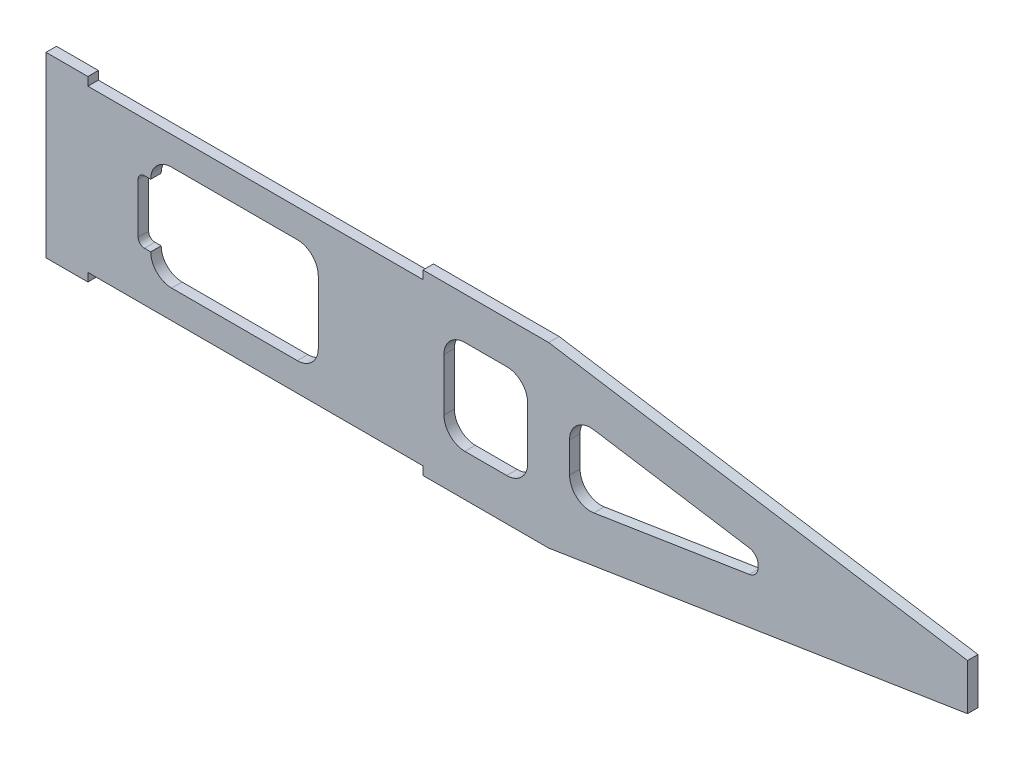
SolidWorks part; units mm, degrees
ref_plane "Ebene vorne" through (0, 0, 0) normal (0, 0, 1) x (1, 0, 0)
ref_plane "Ebene oben" through (0, 0, 0) normal (0, 1, 0) x (1, 0, 0)
ref_plane "Ebene rechts" through (0, 0, 0) normal (1, 0, 0) x (0, 0, -1)
sketch "Skizze1" plane through (0, 0, 0) normal (0, 0, 1) x (1, 0, 0)
  line L0 (0, 0) -> (440, 0) construction
  line L1 (0, 42.5) -> (0, -42.5)
  line L2 (0, -42.5) -> (240, -42.5)
  line L3 (240, -42.5) -> (440, -11)
  line L4 (440, -11) -> (440, 11)
  line L5 (240, 42.5) -> (440, 11)
  line L6 (0, 42.5) -> (240, 42.5)
  dimension "D1" = 440
  dimension "D2" = 85
  dimension "D3" = 22
  dimension "D4" = 200
extrude "Grundplatte" add sketch "Skizze1" along normal blind 5
sketch "Skizze2" plane through (0, 0, 5) normal (0, 0, 1) x (1, 0, 0)
  line L0 (50, 0) -> (44, 0) construction
  line L1 (130, 25) -> (50, 25)
  line L2 (130, 25) -> (130, -25)
  line L3 (130, -25) -> (50, -25)
  line L4 (50, 25) -> (50, 15)
  line L5 (130, 25) -> (50, -25) construction
  line L6 (130, -25) -> (50, 25) construction
  line L7 (44, -15) -> (44, 15)
  line L8 (44, 15) -> (50, 15)
  line L9 (44, -15) -> (50, -15)
  line L10 (50, -15) -> (50, -25)
  point P0 (90, 0)
  dimension "D1" = 90
  dimension "D2" = 50
  dimension "D3" = 80
  dimension "D4" = 30
  dimension "D5" = 6
extrude "Schnitt-Linear austragen1" cut sketch "Skizze2" against normal through all
fillet "Verrundung1" radius 10 4 edges at (130, 25, 2.5) (130, -25, 2.5) (50, 25, 2.5) (50, -25, 2.5)
sketch "Skizze3" plane through (0, 0, 5) normal (0, 0, 1) x (1, 0, 0)
  line L0 (0, 0) -> (440, 0) construction
  line L1 (0, 42.5) -> (0, -42.5) construction
  line L2 (440, -11) -> (440, 11) construction
  line L3 (240, 42.5) -> (0, 42.5) construction
  line L4 (20, 42.5) -> (180, 42.5)
  line L5 (20, 42.5) -> (20, 38.5)
  line L6 (20, 38.5) -> (180, 38.5)
  line L7 (180, 42.5) -> (180, 38.5)
  line L8 (180, -42.5) -> (180, -38.5)
  line L9 (20, -38.5) -> (180, -38.5)
  line L10 (20, -42.5) -> (20, -38.5)
  line L11 (20, -42.5) -> (180, -42.5)
  dimension "D1" = 4
  dimension "D2" = 160
  dimension "D3" = 20
extrude "Ausschnitt_Flächenaufdoppler" cut sketch "Skizze3" against normal through all
sketch "Skizze4" plane through (0, 0, 5) normal (0, 0, 1) x (1, 0, 0)
  line L0 (0, 0) -> (440, 0) construction
  line L1 (440, -11) -> (440, 11) construction
  line L2 (190, -22.5) -> (190, 22.5)
  line L3 (190, 22.5) -> (230, 22.5)
  line L4 (230, 22.5) -> (230, -22.5)
  line L6 (250, -19) -> (250, 19)
  line L7 (250, 19) -> (340, 4.825)
  line L8 (340, 4.825) -> (340, -4.825)
  line L9 (250, -19) -> (340, -4.825)
  line L10 (190, -22.5) -> (230, -22.5)
  line L11 (440, 11) -> (240, 42.5) construction
  line L13 (0, 42.5) -> (0, -42.5) construction
  point P14 (340, 0)
  point P17 (190, 0)
  dimension "D1" = 45
  dimension "D2" = 38
  dimension "D3" = 90
  dimension "D4" = 20
  dimension "D5" = 40
  dimension "D6" = 190
extrude "Ausschnitt Gewicht" cut sketch "Skizze4" against normal through all
fillet "Verrundung2" radius 10 6 edges at (250, -19, 2.5) (250, 19, 2.5) (190, -22.5, 2.5) (230, -22.5, 2.5) (230, 22.5, 2.5) (190, 22.5, 2.5)
fillet "Verrundung3" radius 5 2 edges at (340, -4.825, 2.5) (340, 4.825, 2.5)
fillet "Verrundung4" radius 3 2 edges at (44, -15, 2.5) (44, 15, 2.5)
